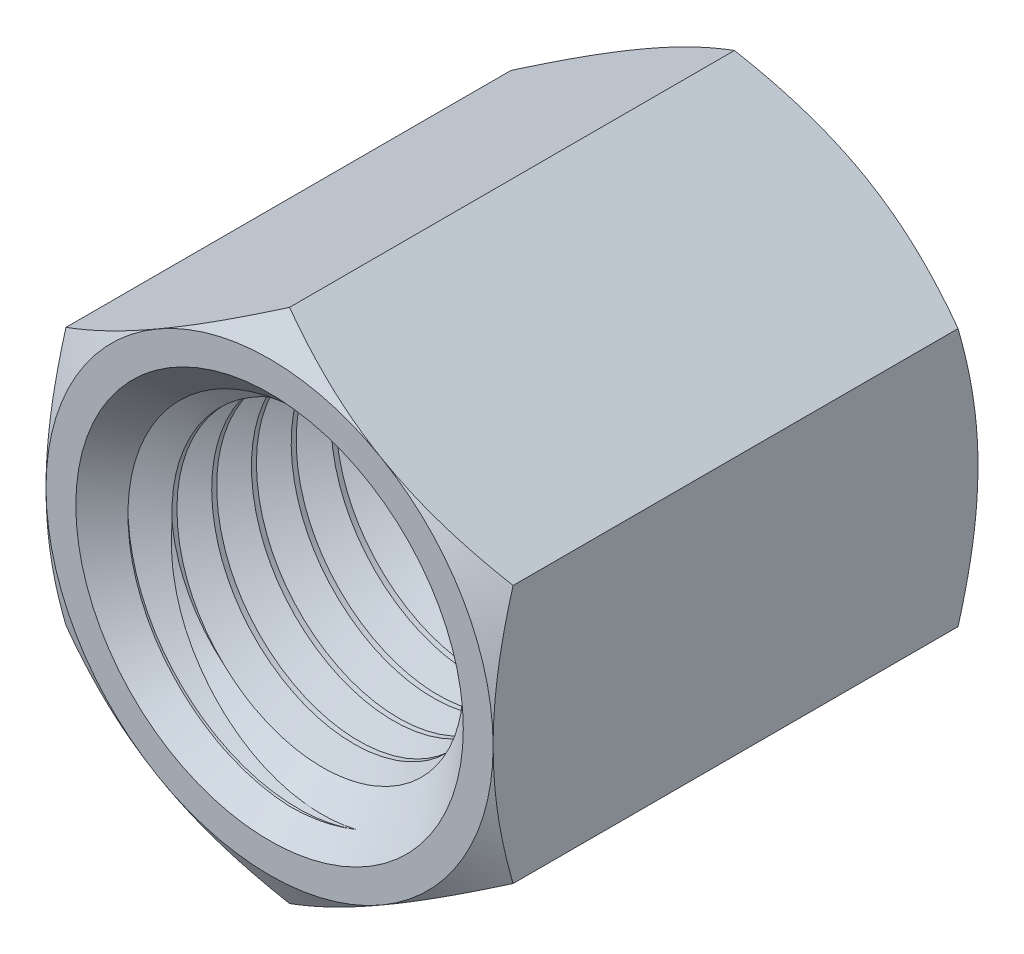
SolidWorks part; units mm, degrees
ref_plane "Front Plane" through (0, 0, 0) normal (0, 0, 1) x (1, 0, 0)
ref_plane "Top Plane" through (0, 0, 0) normal (0, 1, 0) x (1, 0, 0)
ref_plane "Right Plane" through (0, 0, 0) normal (1, 0, 0) x (0, 0, -1)
sketch "Sketch1" plane through (0, 0, 0) normal (1, 0, 0) x (0, 0, -1)
  line L0 (-7.747, 0) -> (7.747, 0) construction
  line L1 (-7.747, 5.5562) -> (-7.747, -5.5562) construction
  line L2 (0, -7.1437) -> (0, 7.1437) construction
  line L3 (7.747, 3.937) -> (7.747, -3.937) construction
  line L4 (-7.747, 5.5562) -> (-9.017, 5.5562) construction
  line L5 (-7.747, 7.1437) -> (7.747, 7.1438) construction
  line L6 (0, 5.5563) -> (4.191, 5.5562) construction
  line L7 (7.747, -3.175) -> (7.747, 3.175)
  line L10 (-7.747, 5.5562) -> (0, 5.5563) construction
  line L11 (4.191, 5.5562) -> (4.191, 3.937) construction
  line L12 (4.191, 3.937) -> (7.747, 3.937) construction
  line L13 (-7.747, -5.5562) -> (0, -5.5563) construction
  line L14 (0, -5.5563) -> (4.191, -5.5562) construction
  line L15 (4.191, -5.5562) -> (4.191, -3.937) construction
  line L16 (4.191, -3.937) -> (7.747, -3.937) construction
  point P2 (0, 0)
  point P6 (-7.747, 0)
  point P9 (0, 0)
  point P12 (7.747, 0)
  point P15 (0, 7.1437)
  point P17 (7.747, -3.937)
  point P30 (7.747, 0)
  dimension "Tube" = 7.874
  dimension "Thread Size" = 11.1125
  dimension "Hex" = 14.2875
  dimension "Length" = 15.494
  dimension "Pitch" = 1.27
  dimension "Shoulder Length" = 3.556
  dimension "For Tube OD" = 6.35
sketch "Sketch1A" plane through (0, 0, 0) normal (0, 0, 1) x (1, 0, 0)
  line L0 (-3.937, 0) -> (3.937, 0) construction
  line L1 (0, 8.2489) -> (-7.1438, 4.1244) construction
  line L2 (-7.1438, 4.1244) -> (-7.1438, -4.1244) construction
  line L3 (-7.1438, -4.1244) -> (0, -8.2489) construction
  line L4 (0, -8.2489) -> (7.1438, -4.1244) construction
  line L5 (7.1438, -4.1244) -> (7.1437, 4.1244) construction
  line L6 (7.1437, 4.1244) -> (0, 8.2489) construction
  line L7 (0, 3.937) -> (0, -3.937) construction
  line L8 (0, -7.1437) -> (0, 7.1437) construction
  circle A0 centre (0, 0) radius 7.1438 construction
  circle A1 centre (0, 0) radius 3.175
  point P1 (0, 0)
  point P15 (0, -5.5562)
ref_plane "Plane1" through (0, 0, 7.747) normal (0, 0, 1) x (1, 0, 0)
sketch "Sketch2" plane through (0, 0, 0) normal (0, 0, 1) x (1, 0, 0)
  line L0 (0, 3.937) -> (0, -3.937) construction
  line L1 (0, 8.2489) -> (-7.1438, 4.1244)
  line L2 (-7.1438, 4.1244) -> (-7.1438, -4.1244)
  line L3 (-7.1438, -4.1244) -> (0, -8.2489)
  line L4 (0, -8.2489) -> (7.1438, -4.1244)
  line L5 (7.1438, -4.1244) -> (7.1438, 4.1244)
  line L6 (7.1438, 4.1244) -> (0, 8.2489)
  circle A0 centre (0, 0) radius 7.1438 construction
  circle A1 centre (0, 0) radius 3.937
extrude "Boss-Extrude1" add sketch "Sketch2" along normal up to vertex (7.747 mm away) and the other way up to vertex (7.747 mm away) up to point (0, 0, 7.747) other way up to point (0, 0, -7.747)
sketch "Sketch3" plane through (0, 0, 0) normal (1, 0, 0) x (0, 0, -1)
  line L0 (-7.747, 5.5562) -> (0, 5.5562) construction
  line L1 (0, -7.1437) -> (0, 7.1437) construction
  line L2 (0, 5.5562) -> (4.191, 5.5562) construction
  line L7 (-7.747, 5.5562) -> (4.191, 5.5562)
  line L8 (4.191, 5.5562) -> (4.191, 3.937)
  line L9 (4.191, 3.937) -> (7.747, 3.937)
  line L10 (-7.747, 5.5562) -> (-7.747, 0)
  line L11 (-7.747, 0) -> (7.747, 0)
  line L12 (7.747, 0) -> (7.747, 3.937)
revolve "Cut-Revolve1" cut sketch "Sketch3" angle 360 about L11
sketch "Sketch4" plane through (0, 0, 7.747) normal (0, 0, 1) x (1, 0, 0)
  circle A0 centre (0, 0) radius 7.1438
extrude "Cut-Extrude1" cut sketch "Sketch4" against normal blind 2.54 draft 60 flip side to cut
mirror "Mirror1" about plane through (0, 0, 0) normal (0, 0, 1) of "Cut-Extrude1"
sketch "Sketch5" plane through (0, 0, 7.747) normal (0, 0, 1) x (1, 0, 0)
  circle A0 centre (0, 0) radius 6.1913
  dimension "D1" = 12.3825
extrude "Cut-Extrude2" cut sketch "Sketch5" against normal through all draft 45
sketch "Sketch6" plane through (0, 0, 7.747) normal (0, 0, 1) x (1, 0, 0)
  circle A0 centre (0, 0) radius 5.5563
curve "Helix/Spiral1" pitch 1.27 height 13.208 radius 5.5563 centre (0, 0, 7.747) axis (0, 0, -1) start towards (0, 1, 0)
sketch "Sketch7" plane through (0, 0, 7.747) normal (0, 0, 1) x (1, 0, 0)
  circle A0 centre (0, 0) radius 6.1913 construction
  circle A1 centre (0, 0) radius 6.1913
extrude "Boss-Extrude2" add sketch "Sketch7" against normal up to surface (11.938 mm away) up to face at (0, -5.5562, -4.191)
sketch "Sketch8" plane through (0, 0, 7.747) normal (0, 0, 1) x (1, 0, 0)
  circle A0 centre (0, 0) radius 5.5562
  dimension "D1" = 11.1125
extrude "Boss-Extrude3" add sketch "Sketch8" against normal up to vertex (11.938 mm away) separate body up to point (0, 5.5562, -4.191)
sketch "Sketch9" plane through (0, 0, 0) normal (1, 0, 0) x (0, 0, -1)
  line L0 (-8.9773, 5.625) -> (-7.7073, 5.625) construction
  line L1 (-7.7073, 5.625) -> (-8.3423, 4.5251) construction
  line L2 (-8.3423, 4.5251) -> (-8.9773, 5.625) construction
  line L3 (-8.3423, 4.5251) -> (-8.3423, 4.6626) construction
  line L4 (-8.3423, 4.6626) -> (-8.3423, 5.4875) construction
  line L5 (-8.3423, 5.4875) -> (-8.3423, 5.625) construction
  line L6 (-8.4217, 4.6626) -> (-8.2629, 4.6626) construction
  line L7 (-7.747, 5.5562) -> (-8.2629, 4.6626)
  line L8 (-7.7867, 5.4875) -> (-8.8979, 5.4875) construction
  line L9 (-8.2629, 4.6626) -> (-8.4217, 4.6626)
  line L10 (-7.747, 5.5562) -> (-8.9376, 5.5562) construction
  line L11 (-8.4217, 4.6626) -> (-8.9376, 5.5562)
  line L12 (-8.9376, 5.5562) -> (-7.747, 5.5562)
  point P12 (-8.3423, 4.6626)
  point P14 (-8.3423, 5.4875)
  point P15 (-8.3423, 5.5563)
  point P16 (-8.3423, 5.5563)
  dimension "D1" = 1.27
  dimension "D2" = 0.1588
sweep "Cut-Sweep1" cut profiles "Sketch9" path "Helix/Spiral1" align with end faces yes
combine bodies "Combine1" operation type subtract main body 111 bodies to subtract 113
sketch "Sketch10" plane through (0, 0, 7.747) normal (0, 0, 1) x (1, 0, 0)
  circle A2 centre (0, 0) radius 6.1913
  circle A3 centre (0, 0) radius 6.1913
  dimension "D1" = 0
extrude "Cut-Extrude3" cut sketch "Sketch10" against normal through all draft 45
equation "\"D3@Helix/Spiral1\"=(\"Length@Sketch1\" - \"Shoulder Length@Sketch1\") + \"Pitch@Sketch1\""
equation "\"D4@Helix/Spiral1\"=\"Pitch@Sketch1\""
equation "\"D1@Sketch9\" = \"Pitch@Sketch1\""
equation "\"D2@Sketch9\" = \"D1@Sketch9\" / 8"
equation "\"D1@Sketch5\" = \"Thread Size@Sketch1\" + \"Pitch@Sketch1\""
equation "\"D1@Sketch8\" = \"Thread Size@Sketch1\""
